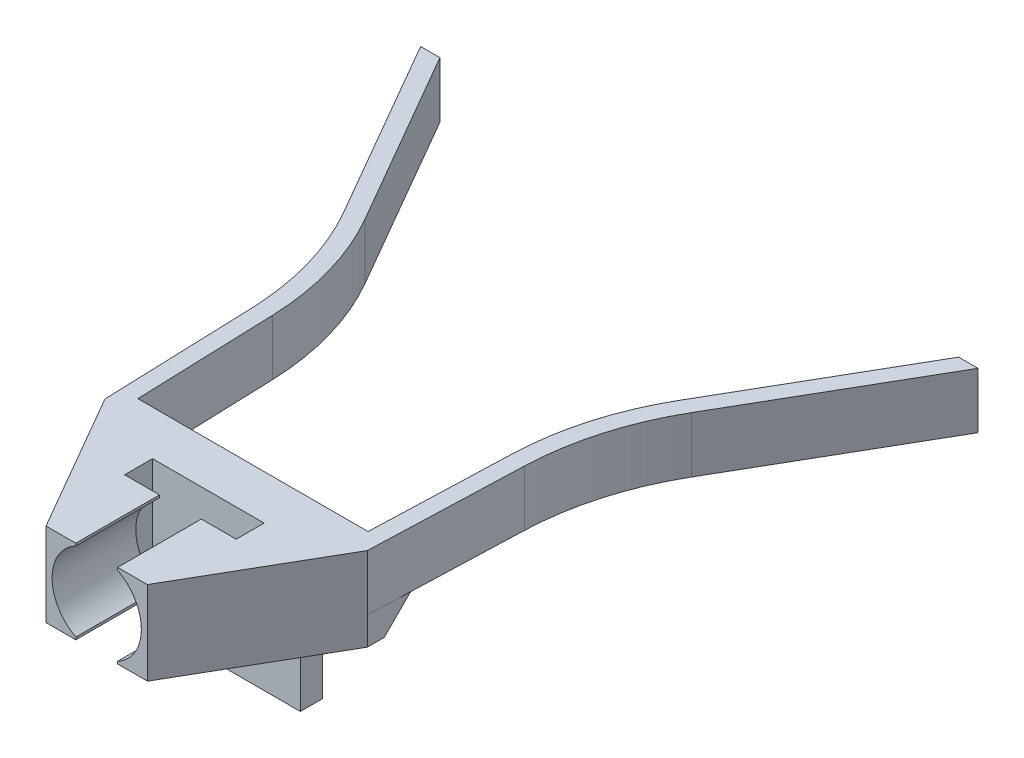
SolidWorks part; units mm, degrees
ref_plane "Front" through (0, 0, 0) normal (0, 0, 1) x (1, 0, 0)
ref_plane "Top" through (0, 0, 0) normal (0, 1, 0) x (1, 0, 0)
ref_plane "Right" through (0, 0, 0) normal (1, 0, 0) x (0, 0, -1)
ref_axis "X" through (-80.9, 0, 0) along (1, 0, 0)
ref_axis "Y" through (0, -50, 0) along (0, 1, 0)
ref_axis "Z" through (0, 0, -80.9) along (0, 0, 1)
sketch "Sketch1" plane through (0, 0, 0) normal (0, 1, 0) x (1, 0, 0)
  line L0 (-8.25, 0) -> (0, 0)
  line L1 (-8.25, 0) -> (-8.7735, 14.9909)
  line L2 (-8.7735, 14.9909) -> (-18.5937, 32)
  line L3 (-18.5937, 32) -> (-19.9794, 32)
  line L5 (0, 0) -> (0, 35.6379) construction
  line L6 (-9.4088, -1.2) -> (0, -1.2)
  line L7 (-9.4088, -1.2) -> (-9.9623, 14.65)
  line L9 (-9.9623, 14.65) -> (-19.9794, 32)
  line L10 (-13.2768, 20.3909) -> (-19.2865, 30.8) construction
  line L11 (-19.2865, 30.8) -> (-21.517, 30.8) construction
  line L12 (-18.5937, 32) -> (-21.517, 32) construction
  line L13 (0, 0) -> (0, -1.2)
  line L14 (-8.7735, 14.9909) -> (-12.2376, 20.9909) construction
  line L15 (-9.9623, 14.65) -> (-13.2768, 20.3909) construction
  line L16 (-12.2376, 20.9909) -> (-18.5937, 32) construction
  point P14 (-12.9221, 17.3927)
  dimension "D1" = 16.5
  dimension "D2" = 15
  dimension "D4" = 30
  dimension "D6" = 32
  dimension "D8" = 2
  dimension "D7" = 1.2
extrude "Boss-Extrude1" add sketch "Sketch1" along normal mid plane 4
mirror "Mirror1" about plane through (0, 2, 0) normal (-1, 0, 0) of "Boss-Extrude1"
sketch "Sketch2" plane through (0, 0, 1.2) normal (0, 0, 1) x (1, 0, 0)
  line L0 (-9.4088, 2) -> (9.4088, 2) construction
  line L1 (-9.4088, 2) -> (9.4088, 2)
  line L2 (-9.4088, 2) -> (-9.4088, -4)
  line L3 (-9.4088, -4) -> (9.4088, -4)
  line L4 (9.4088, 2) -> (9.4088, -4)
  line L5 (-9.4088, 2) -> (9.4088, -4) construction
  line L6 (-9.4088, -4) -> (9.4088, 2) construction
  point P4 (0, -1)
  dimension "D1" = 6
extrude "Boss-Extrude2" add sketch "Sketch2" against normal up to surface (1.2 mm away) and the other way blind 10 up to face at (0, 0, 0)
sketch "Sketch3" plane through (0, 0, 11.2) normal (0, 0, 1) x (1, 0, 0)
  line L0 (0, 0) -> (0, -1) construction
  line L2 (-9.4088, -1) -> (0, -1) construction
  line L3 (-9.4088, 2) -> (-9.4088, -4) construction
  line L4 (-1.5, 1.8267) -> (-1.5, 2)
  line L5 (9.4088, 2) -> (-9.4088, 2) construction
  line L6 (-1.5, 2) -> (1.5, 2)
  line L7 (1.5, 2) -> (1.5, 1.8267)
  line L8 (1.5, -3.8267) -> (1.5, -4)
  line L9 (-9.4088, -4) -> (9.4088, -4) construction
  line L10 (1.5, -4) -> (-1.5, -4)
  line L11 (-1.5, -4) -> (-1.5, -3.8267)
  arc A0 (-1.5, 1.8267) -> (-1.5, -3.8267) centre (0, -1) ccw
  arc A1 (1.5, -3.8267) -> (1.5, 1.8267) centre (0, -1) ccw
  dimension "D1" = 6.4
  dimension "D2" = 3
extrude "Cut-Extrude1" cut sketch "Sketch3" against normal blind 8
sketch "Sketch4" plane through (0, 0, 0) normal (0, 1, 0) x (1, 0, 0)
  line L0 (0, -4.2) -> (0, 0) construction
  line L1 (-4, -3.2) -> (4, -3.2)
  line L2 (-4, -3.2) -> (-4, -5.2)
  line L3 (-4, -5.2) -> (4, -5.2)
  line L4 (4, -3.2) -> (4, -5.2)
  line L5 (-4, -3.2) -> (4, -5.2) construction
  line L6 (-4, -5.2) -> (4, -3.2) construction
  line L7 (8.25, 0) -> (-8.25, 0) construction
  line L9 (1.5, -3.2) -> (-1.5, -3.2) construction
  point P4 (0, -4.2)
  dimension "D1" = 2
  dimension "D2" = 8
extrude "Cut-Extrude2" cut sketch "Sketch4" against normal through all both and the other way through all
chamfer "Chamfer1" distance 2 angle 45 2 edges at (8.8294, -2, 0) (-8.8294, -2, 0)
chamfer "Chamfer2" distance 10 angle 30 2 edges at (9.4088, -1, 11.2) (-9.4088, -1, 11.2) first distance on face at (9.4088, -1.3333, 3.8) first distance on face at (-9.4088, -1.3333, 3.8)
fillet "Fillet1" radius 20 4 edges at (9.9623, 0, -14.65) (8.7735, 0, -14.9909) (-9.9623, 0, -14.65) (-8.7735, 0, -14.9909)
sketch "Sketch5" plane through (0, -4, 0) normal (0, -1, 0) x (1, 0, 0)
  line L0 (8.25, 0) -> (-8.25, 0) construction
  line L1 (5, 0) -> (-5, 0)
  line L2 (5, 0) -> (5, 1.6)
  line L3 (5, 1.6) -> (-5, 1.6)
  line L4 (-5, 0) -> (-5, 1.6)
  line L5 (5, 0) -> (-5, 1.6) construction
  line L6 (5, 1.6) -> (-5, 0) construction
  line L7 (0, 0.8) -> (0, 0) construction
  point P4 (0, 0.8)
  dimension "D1" = 10
  dimension "D2" = 1.6
extrude "Boss-Extrude3" add sketch "Sketch5" along normal blind 12 from surface starting at face at (0, 2, -6.5445)
